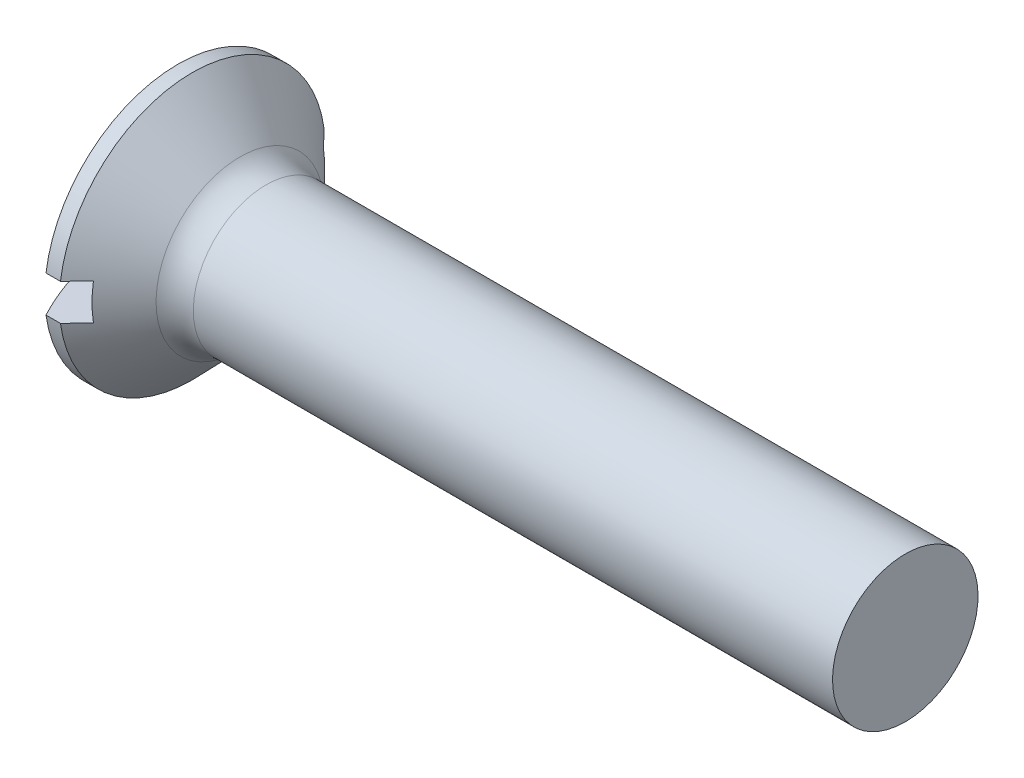
SolidWorks part; units mm, degrees
ref_plane "Front Plane" through (0, 0, 0) normal (0, 0, 1) x (1, 0, 0)
ref_plane "Top Plane" through (0, 0, 0) normal (0, 1, 0) x (1, 0, 0)
ref_plane "Right Plane" through (0, 0, 0) normal (1, 0, 0) x (0, 0, -1)
sketch "BodySke" plane through (0, 0, 0) normal (0, 0, 1) x (1, 0, 0)
  line L0 (2.3, 0) -> (111.3824, 0) construction
  line L1 (2.3, 0) -> (2.3, 9.15) construction
  line L2 (2.3, 9.15) -> (3.2924, 9.15)
  line L3 (3.2924, 9.15) -> (7.3, 5)
  line L4 (7.3, 5) -> (52.3, 5)
  line L5 (52.3, 5) -> (52.3, 0)
  line L6 (8.8, 8.824) -> (8.8, -5.8939) construction
  line L7 (2.3, 0) -> (52.3, 0)
  line L8 (14.3, 8.824) -> (14.3, -4.958) construction
  line L9 (2.3, -9.15) -> (3.2924, -9.15) construction
  line L10 (3.2924, -9.15) -> (7.3, -5) construction
  line L11 (7.3, -5) -> (52.3, -5) construction
  line L12 (2.3, 0) -> (-13.4753, 0) construction
  line L13 (0, 0) -> (0, 11.6167) construction
  line L14 (2.3, 0) -> (0, 0)
  arc A0 (0, 0) -> (2.3, 9.15) centre (19.3505, 0) cw
  point P10 (52.3, 4.172)
  dimension "Thread_minor" = 8.344
  dimension "Length" = 50
  dimension "Head_height" = 5
  dimension "Head_dia" = 18.3
  dimension "Advance" = 1.5
revolve "BaseBody" add sketch "BodySke" angle 360 about L0
cosmetic thread "ThreadCosmetic" [suppressed] parameters "Thread_minor"=8.344
fillet "Fillet1" radius 2.5 1 edges at (7.3, -5, 0)
sketch "SlotSke" plane through (0, 0, 0) normal (1, 0, 0) x (0, 0, -1)
  line L1 (-9.15, 1.25) -> (9.15, 1.25)
  line L2 (-9.15, 1.25) -> (-9.15, -1.25)
  line L3 (-9.15, -1.25) -> (9.15, -1.25)
  line L4 (9.15, 1.25) -> (9.15, -1.25)
  dimension "D1" = 18.3
  dimension "D2" = 9.15
  dimension "D3" = 1.25
extrude "Slot" cut sketch "SlotSke" along normal blind 4.4
sketch "ThdSchSke" plane through (0, 0, 0) normal (0, 0, 1) x (1, 0, 0)
  line L0 (0, 0) -> (55.1256, 0) construction
  line L1 (2.3, 0) -> (111.3824, 0) construction
  line L2 (51.822, 5) -> (51.822, 5.9561)
  line L3 (51.822, 5.9561) -> (52.778, 5.9561)
  line L4 (52.778, 5.9561) -> (52.778, 5)
  line L5 (52.778, 5) -> (52.3, 4.172)
  line L6 (52.3, 4.172) -> (51.822, 5)
  line L7 (7.3, 5) -> (52.3, 5) construction
  line L13 (52.3, 5) -> (52.3, 0) construction
revolve "ThreadSchematic" [suppressed] cut sketch "ThdSchSke" angle 360 about L0
pattern_linear "ThdSchPat" [suppressed] count 25 along (-1, 0, 0) of bodies 103
equation "\"Thread_minor@ThreadCosmetic\" = \"Thread_minor@BodySke\""
equation "\"D1@SlotSke\" = \"Head_dia@BodySke\""
equation "\"D2@SlotSke\" = \"D1@SlotSke\" / 2"
equation "\"D3@SlotSke\" = \"Slot_width@SlotSke\" / 2"
equation "\"Advance@ThdSchPat\" = \"Advance@BodySke\""
equation "\"D1@ThdSchPat\" =  int( \"Thread_length@BodySke\" / \"Advance@ThdSchPat\" ) "
